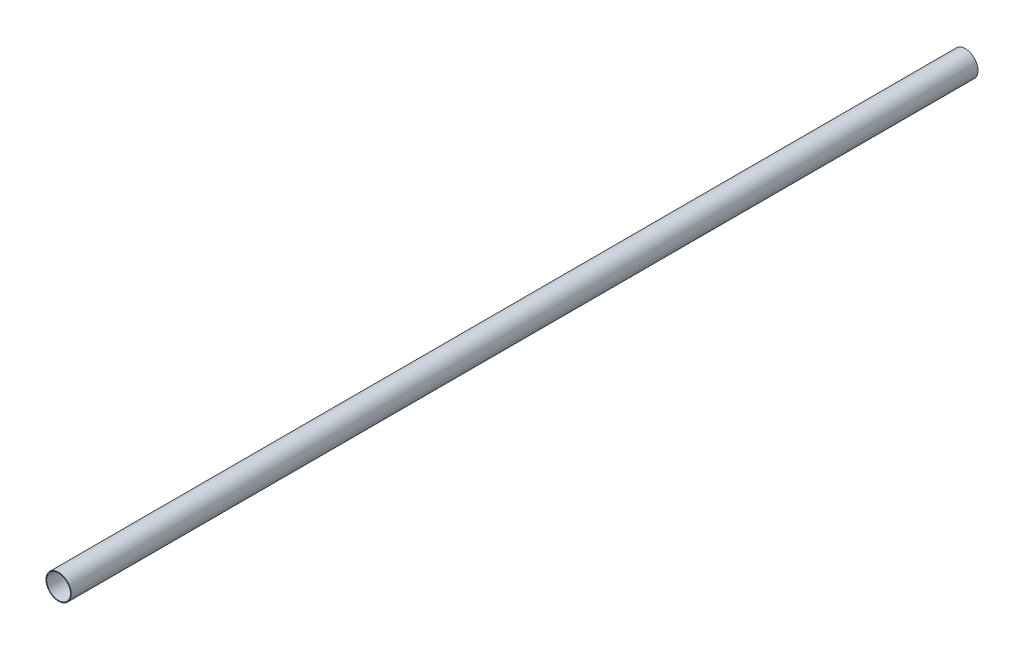
SolidWorks part; units mm, degrees
ref_plane "Front Plane" through (0, 0, 0) normal (0, 0, 1) x (1, 0, 0)
ref_plane "Top Plane" through (0, 0, 0) normal (0, 1, 0) x (1, 0, 0)
ref_plane "Right Plane" through (0, 0, 0) normal (1, 0, 0) x (0, 0, -1)
sketch "Sketch1" plane through (0, 0, 0) normal (0, 0, 1) x (1, 0, 0)
  line L0 (-12.7, 0) -> (12.7, 0) construction
  line L1 (0, 0) -> (0, 1.0456) construction
  point P0 (-11.9888, 0)
  point P4 (0, 0)
  point P6 (11.9888, 0)
  dimension "OD" = 25.4
  dimension "ID" = 23.9776
sketch "Sketch2" plane through (0, 0, 0) normal (0, 0, 1) x (1, 0, 0)
  line L0 (-12.7, 0) -> (12.7, 0) construction
  circle A0 centre (0, 0) radius 11.9888
  circle A1 centre (0, 0) radius 12.7
  dimension "D1" = 23.9776
  dimension "D2" = 25.4
extrude "Boss-Extrude1" add sketch "Sketch2" along normal mid plane 914.4
sketch "Sketch3" plane through (0, 0, 0) normal (1, 0, 0) x (0, 0, -1)
  line L0 (457.2, 0) -> (-457.2, 0) construction
  line L1 (-457.2, 12.7) -> (-457.2, -12.7) construction
  line L2 (0, 0) -> (0, 21.8825) construction
  point P0 (-452.628, 0)
  point P6 (0, 0)
  point P8 (452.628, 0)
  dimension "D1" = 905.256
ref_axis "Center Axis 1" through (0, 0, 457.2) along (0, 0, -1)
ref_plane "Contact Plane 1" through (0, 0, 457.2) normal (0, 0, 1) x (1, 0, 0)
ref_plane "Contact Plane 2" through (0, 0, -457.2) normal (0, 0, -1) x (-1, 0, 0)
equation "\"D1@Sketch2\"=\"ID@Sketch1\""
equation "\"D2@Sketch2\"=\"OD@Sketch1\""
equation "\"D1@Sketch3\"=\"Length@Boss-Extrude1\"*0.99"
